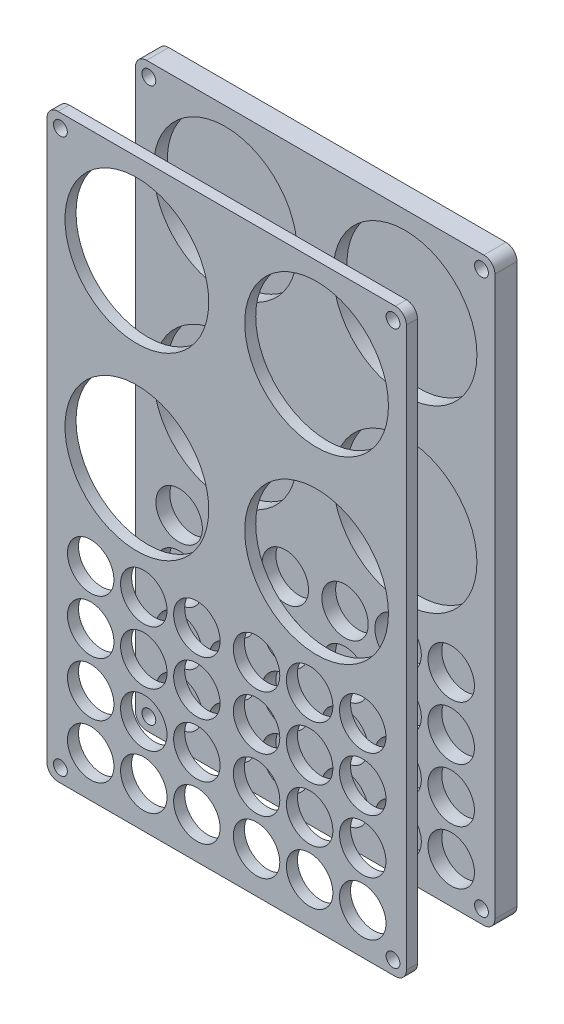
SolidWorks part; units mm, degrees
other "Top Media Holder"
other "Bottom Media Holder"
ref_plane "Front Plane" through (0, 0, 0) normal (1, 0, 0) x (0, 1, 0)
ref_plane "Top Plane" through (0, 0, 0) normal (0, 0, 1) x (0, 1, 0)
ref_plane "Right Plane" through (0, 0, 0) normal (0, 1, 0) x (-1, 0, 0)
sketch "Sketch1" plane through (0, 0, 0) normal (0, 0, 1) x (0, 1, 0)
  line L1 (-105, -65) -> (105, -65)
  line L2 (-105, -65) -> (-105, 65)
  line L3 (-105, 65) -> (105, 65)
  line L4 (105, -65) -> (105, 65)
  line L5 (-105, -65) -> (105, 65) construction
  line L6 (-105, 65) -> (105, -65) construction
  point P0 (0, 0)
  dimension "D1" = 130
  dimension "D2" = 210
extrude "120 x 200 x 67 th" add sketch "Sketch1" along normal blind 40
sketch "Sketch2" plane through (0, 0, 40) normal (0, 0, 1) x (1, 0, 0)
  line L0 (-65, 0) -> (65, 0) construction
  line L1 (-65, 105) -> (-65, -105) construction
  line L2 (65, -105) -> (65, 105) construction
  line L3 (0, 105) -> (0, -105) construction
  line L4 (65, 105) -> (-65, 105) construction
  line L5 (-65, -105) -> (65, -105) construction
  line L6 (-65, 72.5) -> (-58.5, 72.5)
  line L7 (-32.5, 105) -> (-32.5, 98.5)
  line L8 (-6.5, 72.5) -> (0, 72.5)
  line L9 (-65, 40) -> (65, 40) construction
  line L10 (-32.5, 46.5) -> (-32.5, 40)
  line L11 (-62.6582, -100.1582) -> (-65, -100.1582)
  line L12 (-60.1582, -102.6582) -> (-60.1582, -105)
  circle A0 centre (-32.5, 72.5) radius 26
  circle A2 centre (-49.2, -12.1416) radius 8.4 construction
  circle A32 centre (-30, -12.1416) radius 8.4 construction
  circle A33 centre (-10.8, -12.1416) radius 8.4 construction
  circle A34 centre (10.8, -12.1416) radius 8.4 construction
  circle A35 centre (30, -12.1416) radius 8.4 construction
  circle A36 centre (49.2, -12.1416) radius 8.4 construction
  circle A37 centre (10.8, -31.6416) radius 8.4
  circle A38 centre (30, -31.6416) radius 8.4
  circle A39 centre (49.2, -31.6416) radius 8.4
  circle A40 centre (-10.8, -31.6416) radius 8.4
  circle A41 centre (-30, -31.6416) radius 8.4
  circle A42 centre (-49.2, -31.6416) radius 8.4
  circle A43 centre (10.8, -51.1416) radius 8.4
  circle A44 centre (30, -51.1416) radius 8.4
  circle A45 centre (49.2, -51.1416) radius 8.4
  circle A46 centre (-10.8, -51.1416) radius 8.4
  circle A47 centre (-30, -51.1416) radius 8.4
  circle A48 centre (-49.2, -51.1416) radius 8.4
  circle A49 centre (10.8, -70.6416) radius 8.4
  circle A50 centre (30, -70.6416) radius 8.4
  circle A51 centre (49.2, -70.6416) radius 8.4
  circle A52 centre (-10.8, -70.6416) radius 8.4
  circle A53 centre (-30, -70.6416) radius 8.4
  circle A54 centre (-49.2, -70.6416) radius 8.4
  circle A55 centre (10.8, -90.1416) radius 8.4
  circle A56 centre (30, -90.1416) radius 8.4
  circle A57 centre (49.2, -90.1416) radius 8.4
  circle A58 centre (-10.8, -90.1416) radius 8.4
  circle A59 centre (-30, -90.1416) radius 8.4
  circle A60 centre (-49.2, -90.1416) radius 8.4
  circle A61 centre (32.5, 72.5) radius 26
  circle A64 centre (32.5, 7.5) radius 26
  circle A65 centre (-32.5, 7.5) radius 26
  circle A66 centre (-60.1582, -100.1582) radius 2.5
  circle A67 centre (-60.1582, 100.1582) radius 2.5
  circle A68 centre (60.1582, -100.1582) radius 2.5
  circle A69 centre (60.1582, 100.1582) radius 2.5
  point P35 (-32.5, 53)
  dimension "D1" = 52
  dimension "D2" = 3
  dimension "D4" = 5
  dimension "D3" = 5
extrude "16.8 D and 52 D tube holes" cut sketch "Sketch2" against normal blind 37 contours A0 | A61 | A2 | A32 | A33 | A34 | A35 | A36 | A42 | A41 | A40 | A37 | A38 | A39 | A48 | A47 | A46 | A43 | A44 | A45 | A54 | A53 | A52 | A49 | A50 | A51 | A60 | A59 | A58 | A55 | A56 | A57 | A65 | A64 region at (-32.5, 72.5, 40) region at (10.8, -31.6416, 40) region at (30, -31.6416, 40) region at (49.2, -31.6416, 40) region at (-10.8, -31.6416, 40) region at (-30, -31.6416, 40) region at (-49.2, -31.6416, 40) region at (10.8, -51.1416, 40) region at (30, -51.1416, 40) region at (49.2, -51.1416, 40) region at (-10.8, -51.1416, 40) region at (-30, -51.1416, 40) region at (-49.2, -51.1416, 40) region at (10.8, -70.6416, 40) region at (30, -70.6416, 40) region at (49.2, -70.6416, 40) region at (-10.8, -70.6416, 40) region at (-30, -70.6416, 40) region at (-49.2, -70.6416, 40) region at (10.8, -90.1416, 40) region at (30, -90.1416, 40) region at (49.2, -90.1416, 40) region at (-10.8, -90.1416, 40) region at (-30, -90.1416, 40) region at (-49.2, -90.1416, 40) region at (32.5, 72.5, 40) region at (32.5, 7.5, 40) region at (-32.5, 7.5, 40)
fillet "4 mm R filet" radius 4 4 edges at (-65, 105, 20) (65, 105, 20) (-65, -105, 20) (65, -105, 20)
sketch "Sketch3" plane through (0, 0, 0) normal (1, 0, 0) x (0, 1, 0)
  line L0 (-105, 0) -> (-105, 8) construction
  line L1 (-105, 40) -> (-105, 36)
  line L2 (-105, 0) -> (-105, 40) construction
  line L3 (105, 40) -> (105, 0) construction
  line L4 (-105, 8) -> (105, 8)
  line L5 (-105, 8) -> (-105, 36)
  line L6 (-105, 36) -> (105, 36)
  line L7 (105, 8) -> (105, 36)
  line L8 (-105, 8) -> (105, 36) construction
  line L9 (-105, 36) -> (105, 8) construction
  point P11 (0, 22)
  dimension "D1" = 8
  dimension "D2" = 4
extrude "Plate Seperating cut" cut sketch "Sketch3" against normal through all both and the other way through all contours L4 L7 L6 L5 region at (0, 0, 22)
extrude "M4 through holes" cut sketch "Sketch2<3>" against normal through all both and the other way through all contours A66 | A68 | A67 | A69 region at (-60.1582, -100.1582, 40) region at (-60.1582, 100.1582, 40) region at (60.1582, -100.1582, 40) region at (60.1582, 100.1582, 40)
sketch "Sketch2<3>" plane through (0, 0, 40) normal (0, 0, 1) x (1, 0, 0) same geometry as "Sketch2"
